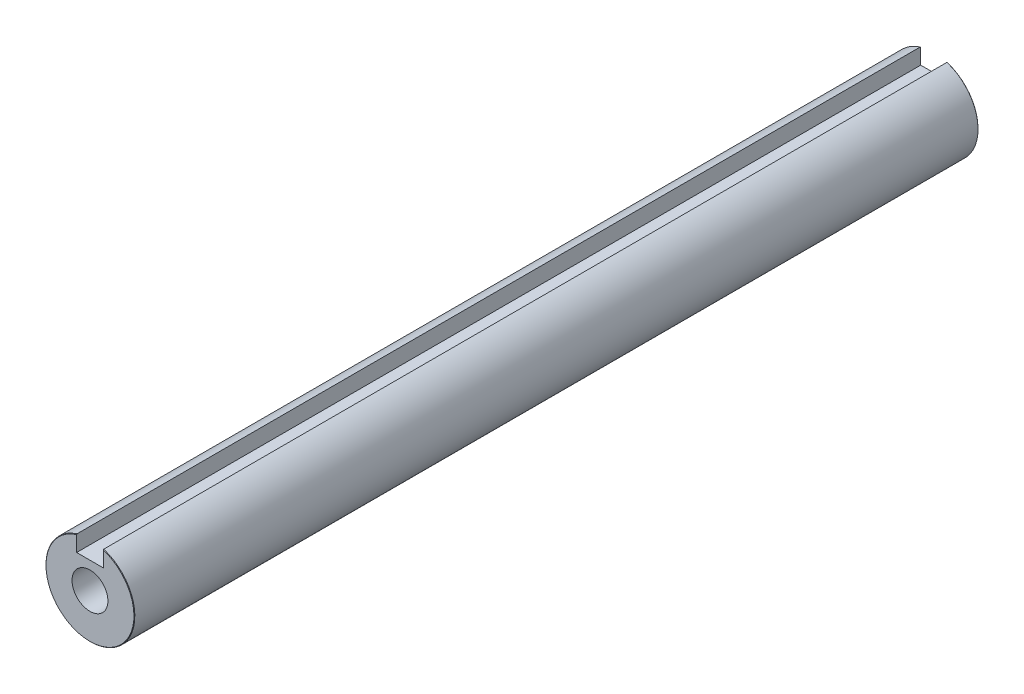
SolidWorks part; units mm, degrees
ref_plane "Front Plane" through (0, 0, 0) normal (0, 0, 1) x (1, 0, 0)
ref_plane "Top Plane" through (0, 0, 0) normal (0, 1, 0) x (1, 0, 0)
ref_plane "Right Plane" through (0, 0, 0) normal (1, 0, 0) x (0, 0, -1)
sketch "Sketch1" plane through (0, 0, 0) normal (1, 0, 0) x (0, 0, -1)
  line L0 (0, 0) -> (0, 5) construction
  line L1 (-47.5, 5) -> (47.5, 5)
  line L2 (-47.5, 5) -> (-47.5, -5)
  line L3 (-47.5, -5) -> (47.5, -5)
  line L4 (47.5, 5) -> (47.5, -5)
  line L5 (-47.5, 5) -> (47.5, -5) construction
  line L6 (-47.5, -5) -> (47.5, 5) construction
  line L7 (0, 0) -> (0, -5) construction
  point P0 (0, 0)
  point P8 (-36, 5)
  point P10 (36, 5)
  point P11 (-32.1667, -5)
  point P12 (34.221, -5)
  dimension "Diameter" = 10
  dimension "Length" = 95
  dimension "D1" = 11.5
  dimension "D2" = 11.5
  dimension "Keyway Length" = 95
  dimension "D3" = 13.279
  dimension "D5" = 15.3333
sketch "Sketch2" plane through (0, 0, 0) normal (0, 0, 1) x (1, 0, 0)
  line L0 (0, 0) -> (0, 5) construction
  line L2 (1.5, 2.9697) -> (-1.5, 2.9697)
  line L3 (1.5, 2.9697) -> (1.5, 4.7697)
  line L4 (1.5, 4.7697) -> (-1.5, 4.7697)
  line L5 (-1.5, 2.9697) -> (-1.5, 4.7697)
  line L6 (1.5, 2.9697) -> (-1.5, 4.7697) construction
  line L7 (1.5, 4.7697) -> (-1.5, 2.9697) construction
  circle A0 centre (0, 0) radius 5
  point P3 (0, 3.8697)
  dimension "Keyway Width" = 3
  dimension "Keyway Depth" = 1.8
sketch "Sketch3" plane through (0, 0, 0) normal (0, 0, 1) x (1, 0, 0)
  line L1 (-1.5, 2.9697) -> (-1.5, 4.7697) construction
  line L2 (1.5, 2.9697) -> (-1.5, 2.9697) construction
  line L3 (1.5, 2.9697) -> (1.5, 4.7697) construction
  line L5 (-1.5, 2.9697) -> (-1.5, 4.7697)
  line L6 (1.5, 2.9697) -> (-1.5, 2.9697)
  line L7 (1.5, 2.9697) -> (1.5, 4.7697)
  circle A0 centre (0, 0) radius 5 construction
  arc A1 (-1.5, 4.7697) -> (1.5, 4.7697) centre (0, 0) ccw
extrude "Boss-Extrude1" add sketch "Sketch3" along normal up to vertex (47.5 mm away) and the other way up to vertex (47.5 mm away) up to point (0, 5, 47.5) other way up to point (0, 5, -47.5)
chamfer "Chamfer1" distance 0.05 angle 45 2 edges at (0, -5, 47.5) (0, -5, -47.5)
hole_wizard "Tap Drill for #10-32 Tap2" positions "3DSketch1" profile "Sketch4" hole size "#10-32" standard "ANSI Inch"
sketch3d "3DSketch1"
  arc A0 (1.5, 4.7173, -47.5) -> (-1.5, 4.7173, -47.5) centre (0, 0, -47.5) ccw construction
  point P0 (0, 0, -47.5)
  point P6 (0, 0, -52.45)
  point P14 (0, 0, 0)
sketch "Sketch4" plane through (0, 0, -47.5) normal (1, 0, 0) x (0, 1, 0)
  line L0 (0, 0) -> (0, 17.0883)
  line L1 (0, 17.0883) -> (2.0193, 15.875)
  line L2 (2.0193, 15.875) -> (2.0193, 0)
  line L5 (2.0193, 0) -> (0, 0)
  line L10 (0, 17.0883) -> (-2.0193, 15.875) construction
  line L11 (0, -6.35) -> (0, 107.95) construction
  dimension "Hole Dia." = 4.0386
  dimension "Hole Depth" = 15.875
  dimension "Drill Angle" = 118
hole_wizard "Tap Drill for #10-32 Tap1" positions "3DSketch2" profile "Sketch5" hole size "#10-32" standard "ANSI Inch"
sketch3d "3DSketch2"
  arc A0 (-1.5, 4.7173, 47.5) -> (1.5, 4.7173, 47.5) centre (0, 0, 47.5) ccw construction
  point P0 (0, 0, 47.5)
  point P6 (0, 0, 52.45)
sketch "Sketch5" plane through (0, 0, 47.5) normal (1, 0, 0) x (0, -1, 0)
  line L0 (0, 0) -> (0, 10.7383)
  line L1 (0, 10.7383) -> (2.0193, 9.525)
  line L2 (2.0193, 9.525) -> (2.0193, 0)
  line L5 (2.0193, 0) -> (0, 0)
  line L10 (0, 10.7383) -> (-2.0193, 9.525) construction
  line L11 (0, -6.35) -> (0, 107.95) construction
  dimension "Hole Dia." = 4.0386
  dimension "Hole Depth" = 9.525
  dimension "Drill Angle" = 118
equation "\"D2@Sketch1\"=1.15*\"Diameter@Sketch1\""
equation "\"D1@Sketch1\"=\"D2@Sketch1\""
equation "\"D1@Chamfer1\"=\"Diameter@Sketch1\"*.005"
equation "\"D3@Sketch1\"=\"D2@Sketch1\"/(2*tan(.5236*180/pi))*4/3"
equation "\"D5@Sketch1\" = 4 / 3 * \"D2@Sketch1\""
